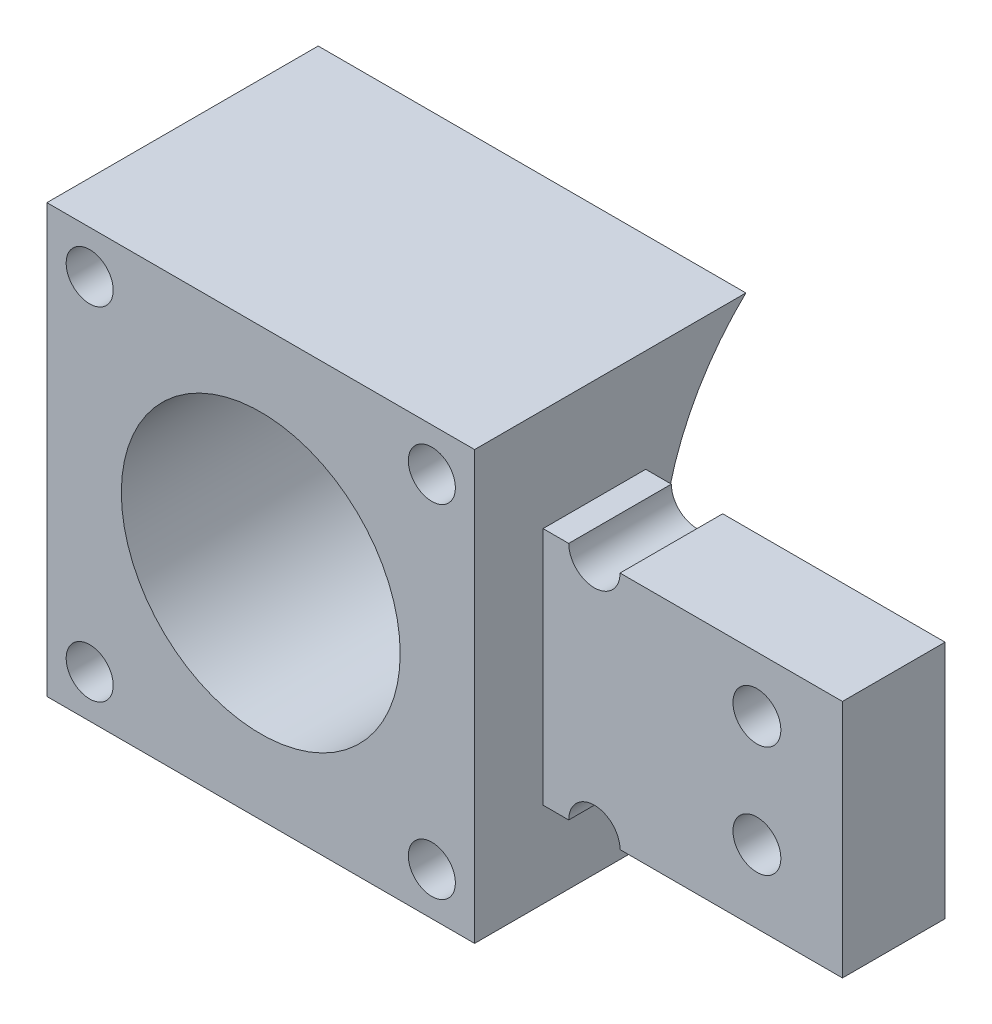
SolidWorks part; units mm, degrees
ref_plane "Front Plane" through (0, 0, 0) normal (0, 0, 1) x (1, 0, 0)
ref_plane "Top Plane" through (0, 0, 0) normal (0, 1, 0) x (1, 0, 0)
ref_plane "Right Plane" through (0, 0, 0) normal (1, 0, 0) x (0, 0, -1)
sketch "Sketch1" plane through (0, 0, 0) normal (0, 0, 1) x (1, 0, 0)
  line L1 (-25, 23) -> (25, 23)
  line L2 (-25, 23) -> (-25, -27)
  line L3 (-25, -27) -> (25, -27)
  line L4 (25, 23) -> (25, -27)
  line L5 (-25, 23) -> (25, -27) construction
  line L6 (-25, -27) -> (25, 23) construction
  circle A0 centre (0, -2) radius 16.3
  circle A1 centre (-20, 18) radius 2.75
  circle A2 centre (20, 18) radius 2.75
  circle A3 centre (20, -22) radius 2.75
  circle A4 centre (-20, -22) radius 2.75
  point P0 (0, -2)
  dimension "D4" = 32.6
  dimension "D6" = 5.5
  dimension "D1" = 2
  dimension "D2" = 50
  dimension "D3" = 50
  dimension "D5" = 20
  dimension "D7" = 20
  dimension "D9" = 20
  dimension "D10" = 20
extrude "Boss-Extrude1" add sketch "Sketch1" along normal blind 53.6
sketch "Sketch2" plane through (0, 0, 0) normal (1, 0, 0) x (0, 0, -1)
  circle A0 centre (0, 0) radius 31.75
  dimension "D1" = 63.5
extrude "Cut-Extrude1" cut sketch "Sketch2" against normal through all and the other way through all
sketch "Sketch3" plane through (-25, 0, 0) normal (-1, 0, 0) x (0, 0, 1)
  line L3 (53.6, 23) -> (21.8875, 23)
  line L4 (16.7052, -27) -> (53.6, -27)
  line L5 (53.6, -27) -> (53.6, 23)
  line L6 (53.6, 23) -> (21.8875, 23)
  line L7 (16.7052, -27) -> (53.6, -27)
  line L8 (53.6, -27) -> (53.6, 23)
  arc A1 (16.7052, -27) -> (21.8875, 23) centre (0, 0) ccw
  arc A2 (16.7052, -27) -> (21.8875, 23) centre (0, 0) ccw
  dimension "D1" = 0
sketch "Sketch4" plane through (25, 0, 0) normal (1, 0, 0) x (0, 0, -1)
  line L3 (-53.6, -27) -> (-16.7052, -27)
  line L4 (-21.8875, 23) -> (-53.6, 23)
  line L5 (-53.6, 23) -> (-53.6, -27)
  line L8 (-53.6, 11) -> (-53.6, -17)
  line L12 (-53.6, 11) -> (-29.7836, 11)
  line L13 (-53.6, 23) -> (-21.8875, 23) construction
  line L14 (0, 0) -> (-85.4701, 0) construction
  line L15 (-53.6, -11) -> (-29.7836, -11) construction
  line L16 (-53.6, -17) -> (-26.8153, -17)
  arc A0 (-21.8875, 23) -> (-16.7052, -27) centre (0, 0) ccw construction
  arc A1 (-21.8875, 23) -> (-16.7052, -27) centre (0, 0) ccw
  arc A2 (-29.7836, 11) -> (-26.8153, -17) centre (0, 0) ccw
  dimension "D3" = 12
  dimension "D4" = 6
  dimension "D1" = 0
extrude "Boss-Extrude3" add sketch "Sketch4" along normal blind 35
sketch "Sketch12" plane through (0, 0, 53.6) normal (0, 0, 1) x (1, 0, 0)
  line L6 (60, 11) -> (60, -17) construction
  line L7 (60, 11) -> (25, 11) construction
  line L8 (60, -17) -> (25, -17) construction
  line L9 (60, 11) -> (60, -17)
  line L10 (60, 11) -> (25, 11)
  line L11 (60, -17) -> (25, -17)
  line L12 (25, 11) -> (25, -17)
extrude "Cut-Extrude7" cut sketch "Sketch12" against normal blind 8
sketch "Sketch9" plane through (0, 0, 0) normal (0, 0, 1) x (1, 0, 0)
  line L0 (31, 11) -> (31, -17) construction
  line L1 (60, 11) -> (25, 11) construction
  line L2 (25, -17) -> (60, -17) construction
  line L3 (25, -27) -> (25, 23) construction
  circle A4 centre (31, 11) radius 3
  circle A5 centre (31, -17) radius 3
  dimension "D1" = 6
  dimension "D2" = 6
extrude "Cut-Extrude5" cut sketch "Sketch9" against normal through all both and the other way through all
sketch "Sketch10" plane through (0, 0, 45.6) normal (0, 0, 1) x (1, 0, 0)
  line L0 (50, 4.5) -> (50, -8.5) construction
  line L1 (60, -2) -> (0, -2) construction
  line L3 (25, -27) -> (25, 23) construction
  line L5 (50, 22) -> (50, -27) construction
  line L6 (-25, -27) -> (25, -27) construction
  line L7 (60, 11) -> (60, -17) construction
  circle A0 centre (50, 4.5) radius 2.8
  circle A1 centre (50, -8.5) radius 2.8
  point P8 (50, -2)
  point P19 (60, -3)
  dimension "D1" = 5.6
  dimension "D2" = 1
  dimension "D3" = 13
  dimension "D4" = 25
extrude "Cut-Extrude6" cut sketch "Sketch10" against normal blind 10 and the other way through all
sketch "Sketch13" plane through (60, 0, 0) normal (1, 0, 0) x (0, 0, -1)
  line L0 (-29.7836, 11) -> (-33.6, 11)
  line L1 (-29.7836, 11) -> (-45.6, 11) construction
  line L2 (-33.6, 11) -> (-33.6, -17)
  line L3 (-45.6, -17) -> (-26.8153, -17) construction
  line L4 (-33.6, -17) -> (-26.8153, -17)
  arc A0 (-29.7836, 11) -> (-26.8153, -17) centre (0, 0) ccw construction
  arc A1 (-29.7836, 11) -> (-26.8153, -17) centre (0, 0) ccw
  dimension "D1" = 33.6
extrude "Cut-Extrude8" cut sketch "Sketch13" against normal up to surface (35 mm away) up to face at (25, -2.5151, 36.8558)
